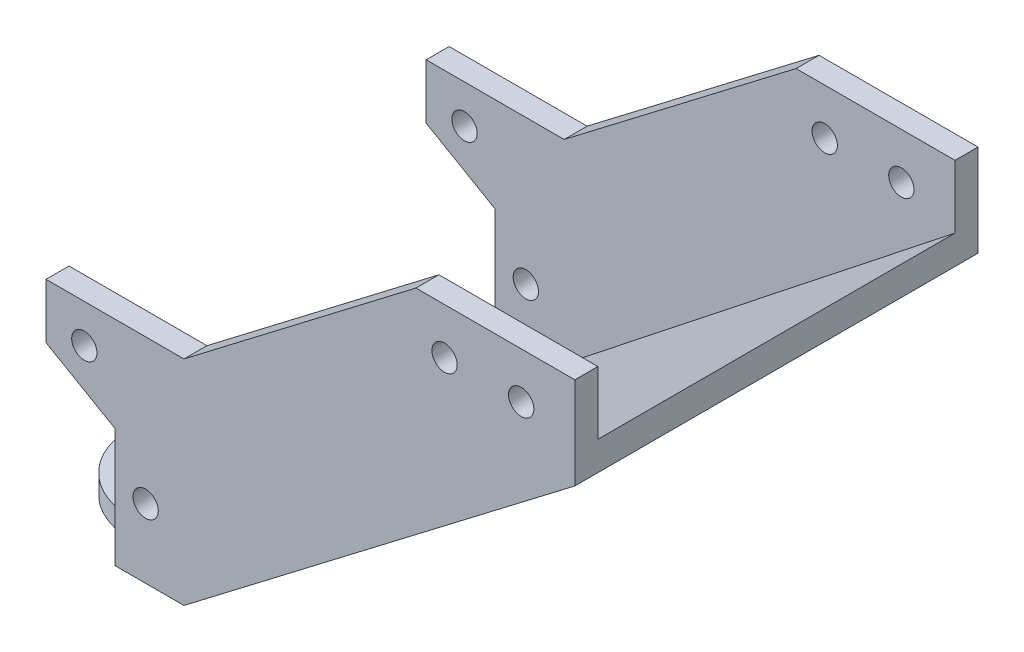
SolidWorks part; units mm, degrees
material "ABS"
ref_plane "Front Plane" through (0, 0, 0) normal (0, 0, 1) x (1, 0, 0)
ref_plane "Top Plane" through (0, 0, 0) normal (0, 1, 0) x (1, 0, 0)
ref_plane "Right Plane" through (0, 0, 0) normal (1, 0, 0) x (0, 0, -1)
sketch "Sketch1" plane through (0, 0, 0) normal (0, 0, 1) x (1, 0, 0)
  line L1 (-13, 18.8564) -> (-13, 11.6962)
  line L2 (-13, 11.6962) -> (-4, 6.5)
  line L3 (-4, 6.5) -> (-4, -9)
  line L4 (-4, -9) -> (5, -9)
  line L5 (5, -9) -> (5, 18.8564)
  line L7 (-8, 13.8564) -> (0, 0) construction
  line L8 (-13, 18.8564) -> (5, 18.8564)
  line L9 (57, 42) -> (57, 30) construction
  line L10 (5, -9) -> (56, 30)
  line L11 (56, 30) -> (56, 42)
  line L12 (56, 42) -> (35.2647, 42)
  line L13 (35.2647, 42) -> (5, 18.8564)
  line L14 (-4, -6.5) -> (5, -6.5)
  line L15 (5, -6.5) -> (56, 33.7766)
  circle A0 centre (0, 0) radius 1.65
  circle A1 centre (-8, 13.8564) radius 1.65
  circle A2 centre (49, 36) radius 1.65
  circle A3 centre (39, 36) radius 1.65
  dimension "D2" = 3.3
  dimension "D15" = 3.3
  dimension "D1" = 16
  dimension "D3" = 60
  dimension "D4" = 5
  dimension "D5" = 9
  dimension "D6" = 5
  dimension "D7" = 4
  dimension "D8" = 6.5
  dimension "D9" = 5
  dimension "D10" = 120
  dimension "D11" = 12
  dimension "D12" = 52
  dimension "D13" = 51
  dimension "D14" = 1
  dimension "D16" = 6
  dimension "D17" = 10
  dimension "D18" = 7
  dimension "D19" = 2.5
  dimension "D20" = 3
extrude "Boss-Extrude1" add sketch "Sketch1" along normal blind 3 contours L8 L1 L2 L3 L4 L5 A1 A0 | L12 L13 L5 L10 L11 | L15 L5 L10 L11 | L14 L3 L4 L5 region at (-1.7694, 8.3928, 0) region at (27.1978, 22.3965, 0) region at (32.2289, 13.4129, 0) region at (0.5, -7.75, 0)
extrude "Boss-Extrude2" add sketch "Sketch1<3>" against normal blind 46.6 contours L14 L3 L4 L5 | L15 L5 L10 L11 region at (32.2289, 13.4129, 0) region at (0.5, -7.75, 0)
sketch "Sketch1<3>" plane through (0, 0, 0) normal (0, 0, 1) x (1, 0, 0) same geometry as "Sketch1"
extrude "Boss-Extrude3" add sketch "Sketch1<4>" against normal blind 3 from surface contours L3 L14 L5 L8 L1 L2 A1 A0 | L14 L3 L4 L5 | L15 L5 L10 L11 | L5 L15 L11 L12 L13 A3 A2 region at (-1.7694, 8.3928, 0) region at (27.1978, 22.3965, 0) region at (32.2289, 13.4129, 0) region at (0.5, -7.75, 0) starting at face at (19, 5.4628, -46.6)
sketch "Sketch1<4>" plane through (0, 0, 0) normal (0, 0, 1) x (1, 0, 0) same geometry as "Sketch1"
sketch "Sketch2" plane through (0, -9, 0) normal (0, -1, 0) x (1, 0, 0)
  line L0 (1, -23.3) -> (-1, -23.3) construction
  line L1 (1, -24.95) -> (-1, -24.95)
  line L2 (1, -21.65) -> (-1, -21.65)
  line L3 (-4, 3) -> (-4, -49.6) construction
  arc A0 (1, -24.95) -> (1, -21.65) centre (1, -23.3) ccw
  arc A1 (-1, -21.65) -> (-1, -24.95) centre (-1, -23.3) ccw
  point P2 (0, -23.3)
  point P9 (-4, -23.3)
  dimension "D1" = 4
  dimension "D2" = 3.3
  dimension "D3" = 2
extrude "Cut-Extrude1" cut sketch "Sketch2" against normal blind 88.5
sketch "Sketch3" plane through (-4, 0, 0) normal (-1, 0, 0) x (0, 0, 1)
  line L0 (-46.6, -6.5) -> (0, -6.5) construction
  line L1 (-45.6, -6.5) -> (-1, -6.5)
  line L2 (-45.6, -6.5) -> (-45.6, -9)
  line L3 (-45.6, -9) -> (-1, -9)
  line L4 (-1, -6.5) -> (-1, -9)
  line L5 (3, -9) -> (-49.6, -9) construction
  dimension "D1" = 1
  dimension "D2" = 1
extrude "Boss-Extrude4" add sketch "Sketch3" along normal blind 12
fillet "Fillet1" radius 10 2 edges at (-16, -7.75, -1) (-16, -7.75, -45.6)
hole_wizard "CSK SLOT for M3 Countersunk Flat Head Screw1" positions "Sketch4" profile "Sketch5" size "M3" standard "ISO" slot yes end condition up to next
sketch "Sketch4" plane through (0, -9, 0) normal (0, -1, 0) x (-1, 0, 0)
  line L0 (-5, -3) -> (-5, 49.6) construction
  line L1 (-1, 21.65) -> (1, 21.65) construction
  line L2 (2.5, 23.3) -> (-2.5, 23.3) construction
  point P0 (0, 23.3)
  point P6 (-5, 23.3)
  point P9 (0, 21.65)
  dimension "D1" = 5
sketch "Sketch5" plane through (0, -9, -23.3) normal (1, 0, 0) x (0, 0, -1)
  line L0 (0, 0) -> (0, 51)
  line L1 (0, 51) -> (1.825, 51)
  line L2 (1.8, 50.975) -> (1.8, 1.35)
  line L3 (1.8, 1.35) -> (3.15, 0)
  line L5 (3.15, 0) -> (0, 0)
  line L6 (-1.8, 1.35) -> (-3.15, 0) construction
  line L7 (1.825, 51) -> (1.8, 50.975)
  line L8 (-1.825, 51) -> (-1.8, 50.975) construction
  line L11 (0, -6.35) -> (0, 107.95) construction
  dimension "Thru Hole Dia." = 3.6
  dimension "Thru Hole Depth" = 51
  dimension "Near C'Sink Dia." = 6.3
  dimension "Near C'Sink Angle" = 90
  dimension "Far C'Sink Dia." = 3.65
  dimension "Far C'Sink Angle" = 90
equation "\"D1@Sketch3\"=\"D2@Sketch3\""
